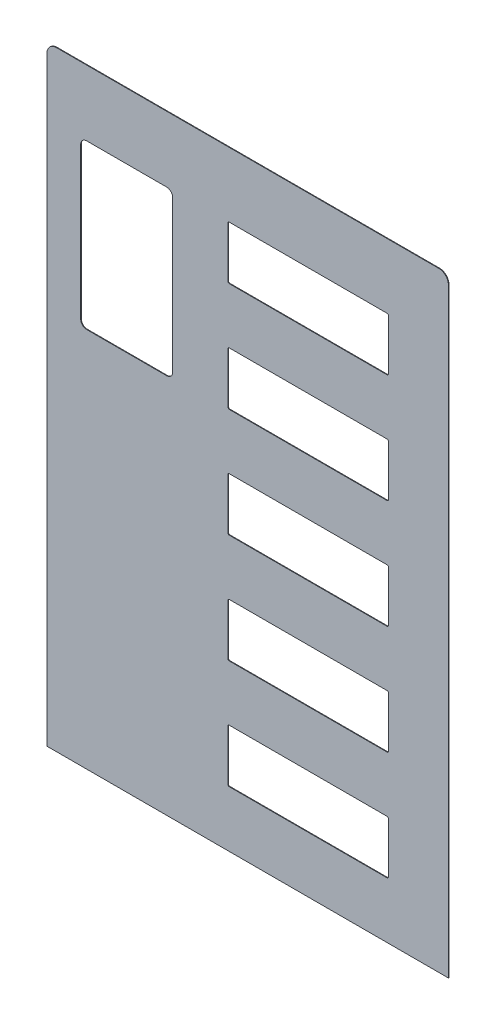
SolidWorks part; units mm, degrees
ref_plane "Front Plane" through (0, 0, 0) normal (0, 0, 1) x (1, 0, 0)
ref_plane "Top Plane" through (0, 0, 0) normal (0, 1, 0) x (1, 0, 0)
ref_plane "Right Plane" through (0, 0, 0) normal (1, 0, 0) x (0, 0, -1)
sketch "Sketch1" plane through (0, 0, 0) normal (0, 0, 1) x (1, 0, 0)
  line L1 (0, 0) -> (663.4, 0)
  line L2 (0, 0) -> (0, 992)
  line L3 (15.7, 1007.7) -> (647.7, 1007.7)
  line L4 (663.4, 0) -> (663.4, 992)
  arc A0 (647.7, 1007.7) -> (663.4, 992) centre (647.7, 992) cw
  arc A1 (0, 992) -> (15.7, 1007.7) centre (15.7, 992) cw
  dimension "D3" = 15.7
  dimension "D1" = 663.4
  dimension "D2" = 1007.7
base flange "Base-Flange1" sketch "Sketch1" thickness 1 reverse thickness direction no parameters "D1"=1
edge flange "Edge-Flange1" [suppressed] sketch "Sketch8" flange angle 90 flange position material inside bend radius 1 thickness 1
sketch "Sketch8" plane through (0, 0, -1) normal (0, -1, 0) x (-1, 0, 0)
  line L0 (0, 0) -> (-822, 0) construction
  line L1 (-42, 0) -> (-780, 0)
  line L2 (-780, 0) -> (-780, 12)
  line L3 (-780, 12) -> (-42, 12)
  line L4 (-42, 12) -> (-42, 0)
  line L5 (0, 0) -> (0, -1) construction
  line L6 (-822, 0) -> (-822, -1) construction
  circle A0 centre (-81, 6) radius 2.75
  circle A1 centre (-261, 6) radius 2.75
  circle A2 centre (-441, 6) radius 2.75
  circle A3 centre (-621, 6) radius 2.75
  circle A4 centre (-801, 6) radius 2.75
  circle A5 centre (-981, 6) radius 2.75
  circle A6 centre (-1161, 6) radius 2.75
  point P6 (-42, 6)
  dimension "D1" = 5.5
  dimension "D2" = 39
  dimension "D4" = 42
  dimension "D5" = 42
  dimension "D3" = 7
bend "EdgeBend1" bend radius 1 bend angle 90 parameters "D5"=1, "D6"=10, "D7"=12
sketch "Sketch9" plane through (0, 0, 0) normal (0, 0, 1) x (1, 0, 0)
  line L0 (663.4, 0) -> (663.4, 992) construction
  line L1 (562.2, 900.7) -> (301.2, 900.7)
  line L2 (564.2, 898.7) -> (564.2, 814.7)
  line L3 (562.2, 812.7) -> (301.2, 812.7)
  line L4 (299.2, 898.7) -> (299.2, 814.7)
  line L5 (647.7, 1007.7) -> (15.7, 1007.7) construction
  line L38 (564.2, 718.7) -> (564.2, 634.7)
  line L39 (562.2, 720.7) -> (301.2, 720.7)
  line L40 (562.2, 632.7) -> (301.2, 632.7)
  line L41 (299.2, 718.7) -> (299.2, 634.7)
  line L42 (564.2, 538.7) -> (564.2, 454.7)
  line L43 (562.2, 540.7) -> (301.2, 540.7)
  line L44 (562.2, 452.7) -> (301.2, 452.7)
  line L45 (299.2, 538.7) -> (299.2, 454.7)
  line L46 (564.2, 358.7) -> (564.2, 274.7)
  line L47 (562.2, 360.7) -> (301.2, 360.7)
  line L48 (562.2, 272.7) -> (301.2, 272.7)
  line L49 (299.2, 358.7) -> (299.2, 274.7)
  line L74 (564.2, 178.7) -> (564.2, 94.7)
  line L75 (562.2, 180.7) -> (301.2, 180.7)
  line L76 (562.2, 92.7) -> (301.2, 92.7)
  line L77 (299.2, 178.7) -> (299.2, 94.7)
  arc A0 (564.2, 814.7) -> (562.2, 812.7) centre (562.2, 814.7) cw
  arc A1 (301.2, 812.7) -> (299.2, 814.7) centre (301.2, 814.7) cw
  arc A2 (301.2, 900.7) -> (299.2, 898.7) centre (301.2, 898.7) ccw
  arc A3 (562.2, 900.7) -> (564.2, 898.7) centre (562.2, 898.7) cw
  arc A36 (562.2, 720.7) -> (564.2, 718.7) centre (562.2, 718.7) cw
  arc A37 (564.2, 634.7) -> (562.2, 632.7) centre (562.2, 634.7) cw
  arc A38 (301.2, 632.7) -> (299.2, 634.7) centre (301.2, 634.7) cw
  arc A39 (301.2, 720.7) -> (299.2, 718.7) centre (301.2, 718.7) ccw
  arc A40 (562.2, 540.7) -> (564.2, 538.7) centre (562.2, 538.7) cw
  arc A41 (564.2, 454.7) -> (562.2, 452.7) centre (562.2, 454.7) cw
  arc A42 (301.2, 452.7) -> (299.2, 454.7) centre (301.2, 454.7) cw
  arc A43 (301.2, 540.7) -> (299.2, 538.7) centre (301.2, 538.7) ccw
  arc A44 (562.2, 360.7) -> (564.2, 358.7) centre (562.2, 358.7) cw
  arc A45 (564.2, 274.7) -> (562.2, 272.7) centre (562.2, 274.7) cw
  arc A46 (301.2, 272.7) -> (299.2, 274.7) centre (301.2, 274.7) cw
  arc A47 (301.2, 360.7) -> (299.2, 358.7) centre (301.2, 358.7) ccw
  arc A72 (562.2, 180.7) -> (564.2, 178.7) centre (562.2, 178.7) cw
  arc A73 (564.2, 94.7) -> (562.2, 92.7) centre (562.2, 94.7) cw
  arc A74 (301.2, 92.7) -> (299.2, 94.7) centre (301.2, 94.7) cw
  arc A75 (301.2, 180.7) -> (299.2, 178.7) centre (301.2, 178.7) ccw
  dimension "D5" = 2
  dimension "D1" = 99.2
  dimension "D2" = 265
  dimension "D3" = 88
  dimension "D4" = 107
  dimension "D6" = 1
  dimension "D7" = 5
extrude "Cut-Extrude1" cut sketch "Sketch9" against normal blind 10 normal cut yes
sketch "Sketch10" plane through (0, 0, 0) normal (0, 0, 1) x (1, 0, 0)
  line L1 (65.7, 629.2) -> (197.7, 629.2)
  line L2 (55.7, 639.2) -> (55.7, 889.2)
  line L3 (65.7, 899.2) -> (197.7, 899.2)
  line L4 (207.7, 639.2) -> (207.7, 889.2)
  line L6 (663.4, 0) -> (663.4, 992) construction
  line L8 (647.7, 1007.7) -> (15.7, 1007.7) construction
  arc A0 (65.7, 629.2) -> (55.7, 639.2) centre (65.7, 639.2) cw
  arc A1 (197.7, 629.2) -> (207.7, 639.2) centre (197.7, 639.2) ccw
  arc A2 (55.7, 889.2) -> (65.7, 899.2) centre (65.7, 889.2) cw
  arc A3 (197.7, 899.2) -> (207.7, 889.2) centre (197.7, 889.2) cw
  dimension "D5" = 10
  dimension "D1" = 152
  dimension "D2" = 270
  dimension "D3" = 108.5
  dimension "D4" = 455.7
extrude "Cut-Extrude2" cut sketch "Sketch10" against normal blind 10 normal cut yes
sketch "Bend-Lines1" [suppressed] plane through (0, 0, 0) normal (0, 1, 0) x (1, 0, 0)
sketch "Bounding-Box1" [suppressed] plane through (0, 0, 0) normal (0, 1, 0) x (1, 0, 0)
sheet metal parameters "Sheet-Metal1" thickness 1 parameters "D1"=2
flat pattern "Flat-Pattern1" [suppressed]
sketch "Bend-Lines2" plane through (0, 0, 0) normal (0, 1, 0) x (1, 0, 0)
sketch3d "Bounding-Box2" [suppressed]
  line L0 (15, 15, 0) -> (-1227, 15, 0) construction
  line L1 (15, -935, 0) -> (-1227, -935, 0) construction
  line L2 (15, 15, 0) -> (15, -935, 0) construction
  line L3 (-1227, 15, 0) -> (-1227, -935, 0) construction
sheet metal parameters "Sheet-Metal2" thickness 1 parameters "D1"=2
flat pattern "Flat-Pattern1"
sketch "Bend-Lines2" plane through (0, 0, 0) normal (0, 0, 1) x (1, 0, 0)
  line L0 (0, 0.8219) -> (1242, 0.8219) construction
  line L1 (0, 0.8219) -> (1242, 0.8219) construction
sketch3d "Bounding-Box2" [suppressed]
  line L0 (-15, 15, 0) -> (1227, 15, 0) construction
  line L1 (-15, -946.3562, 0) -> (1227, -946.3562, 0) construction
  line L2 (-15, 15, 0) -> (-15, -946.3562, 0) construction
  line L3 (1227, 15, 0) -> (1227, -946.3562, 0) construction
bend of the flat pattern "Flatten-<EdgeBend1>1"
sheet metal parameters "Sheet-Metal3" thickness 1 parameters "D1"=2
flat pattern "Flat-Pattern1"
sketch "Bend-Lines2" plane through (0, 0, 0) normal (0, 0, 1) x (1, 0, 0)
  line L0 (0, 0.8219) -> (1244, 0.8219) construction
  line L1 (0, 0.8219) -> (1244, 0.8219) construction
sketch3d "Bounding-Box2" [suppressed]
  line L0 (-16, 16, 0) -> (1228, 16, 0) construction
  line L1 (-16, -945.3562, 0) -> (1228, -945.3562, 0) construction
  line L2 (-16, 16, 0) -> (-16, -945.3562, 0) construction
  line L3 (1228, 16, 0) -> (1228, -945.3562, 0) construction
sheet metal parameters "Sheet-Metal4" thickness 1 parameters "D1"=2
flat pattern "Flat-Pattern1"
sketch "Bend-Lines2" plane through (0, 0, 0) normal (0, 0, 1) x (1, 0, 0)
sketch3d "Bounding-Box2" [suppressed]
  line L0 (647.7, -992, 0) -> (647.7, 15.7, 0) construction
  line L1 (-15.7, -992, 0) -> (-15.7, 15.7, 0) construction
  line L2 (647.7, -992, 0) -> (-15.7, -992, 0) construction
  line L3 (647.7, 15.7, 0) -> (-15.7, 15.7, 0) construction
equation "\"D5@Sketch8\"=\"D4@Sketch8\""
